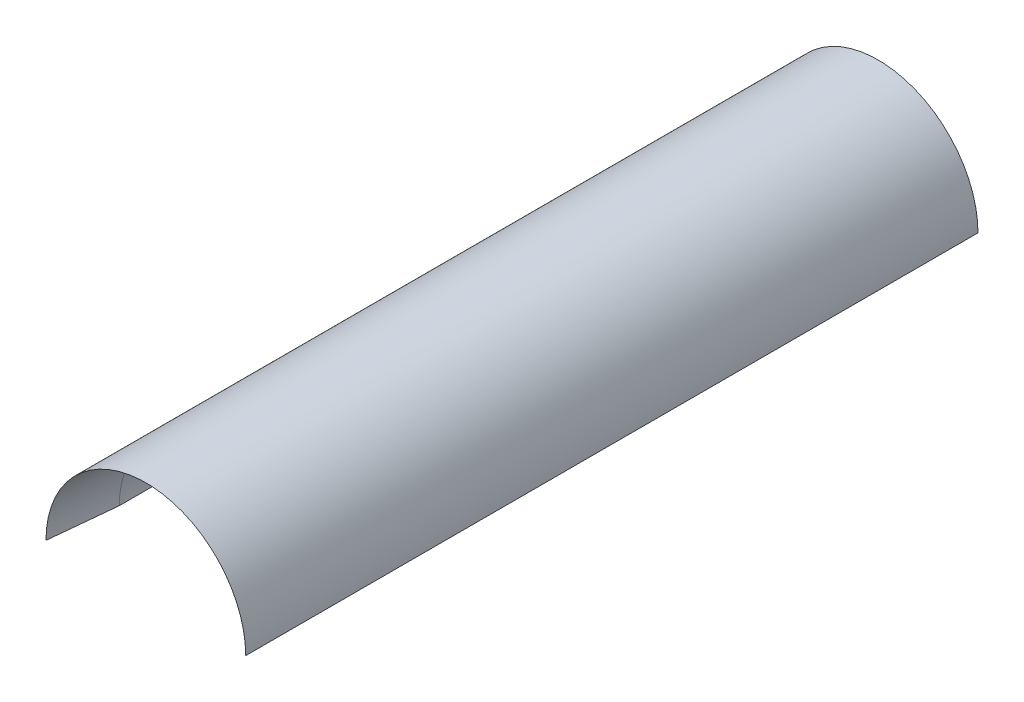
SolidWorks part; units mm, degrees
ref_plane "Front Plane" through (0, 0, 0) normal (0, 0, 1) x (1, 0, 0)
ref_plane "Top Plane" through (0, 0, 0) normal (0, 1, 0) x (1, 0, 0)
ref_plane "Right Plane" through (0, 0, 0) normal (1, 0, 0) x (0, 0, -1)
sketch "Sketch1" plane through (0, 0, 0) normal (0, 0, 1) x (1, 0, 0)
  line L0 (-30, 0) -> (-28, 0)
  line L1 (30, 0) -> (28, 0)
  arc A0 (30, 0) -> (-30, 0) centre (0, 0) ccw
  arc A1 (28, 0) -> (-28, 0) centre (0, 0) ccw
  dimension "D1" = 30
  dimension "D2" = 60
  dimension "D3" = 2
extrude "Boss-Extrude1" add sketch "Sketch1" along normal blind 220 contours A1 L1 A0 L0 region at (0, 29.3292, 0)
chamfer "Chamfer1" distance 2 distance2 20 1 edges at (0, 28, 220) first distance on face at (0, 14.5, 220)
